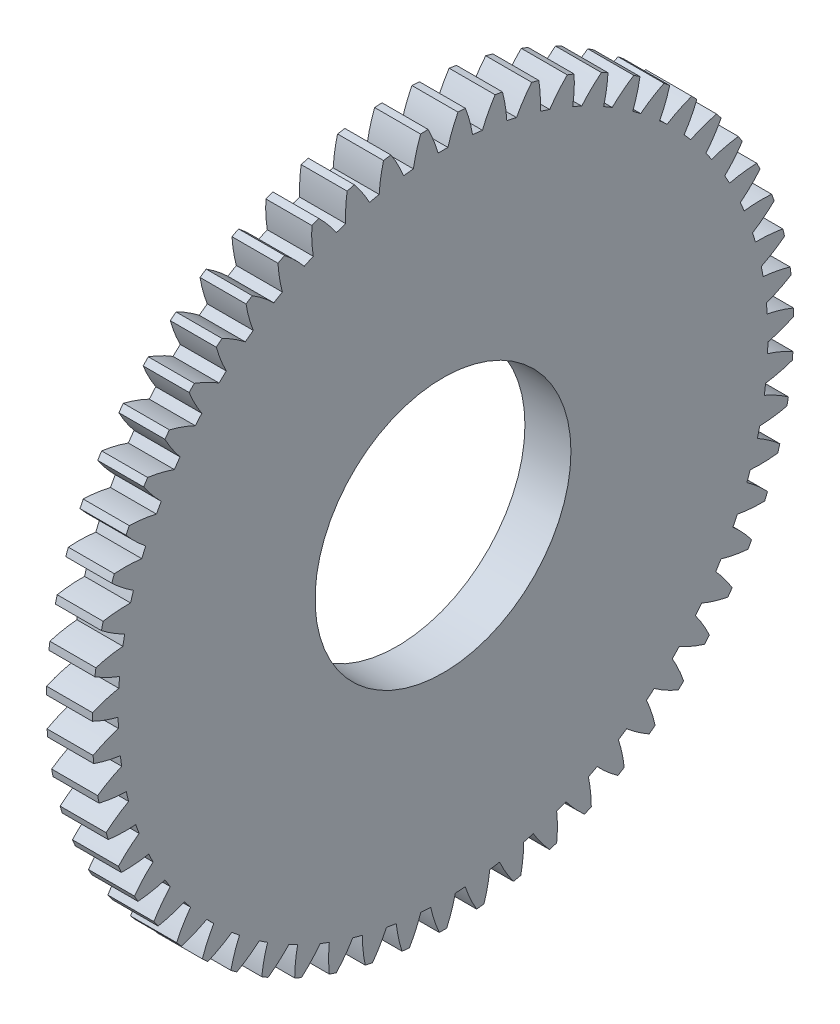
SolidWorks part; units mm, degrees
ref_plane "Plane1" through (0, 0, 0) normal (0, 0, 1) x (1, 0, 0)
ref_plane "Plane2" through (0, 0, 0) normal (0, 1, 0) x (1, 0, 0)
ref_plane "Plane3" through (0, 0, 0) normal (1, 0, 0) x (0, 0, -1)
sketch "HoldingSke" plane through (0, 0, 0) normal (0, 1, 0) x (1, 0, 0)
  line L0 (0, 0) -> (0.515, -0.8572)
  line L1 (-15, 0) -> (100, 0) construction
  line L2 (0, 0) -> (-2.1039, 2.3779)
  line L3 (0, 0) -> (-11.863, 4.5341)
  line L4 (0, 0) -> (4.4479, 7.4025)
  line L5 (0, 0) -> (-46.8476, -17.4728)
  line L6 (0, 0) -> (-3.3159, -2.2372)
  line L7 (-2.1039, 2.3779) -> (8.6586, 51.2059)
  line L8 (-76.2, 54.61) -> (-74.8, 54.61)
  line L9 (-71.009, 38.7566) -> (-53.1078, 45.2721)
  line L10 (-76.2, 71.12) -> (104.1128, 71.12)
  line L11 (0, 0) -> (-4, 0)
  line L12 (-76.2, 101.6) -> (-76.162, 101.6)
  line L13 (24.9733, 27.94) -> (52.9518, 28.4284)
  line L14 (24.9733, 27.94) -> (24.9743, 27.94)
  line L15 (24.9733, 27.94) -> (100.4006, 29.5858)
  line L16 (-63.627, -1) -> (-12.827, -1)
  circle A0 centre (0, 0) radius 4
  circle A1 centre (0, 0) radius 28.249
  circle A2 centre (0, 0) radius 37.5
  circle A3 centre (0, 0) radius 4
  dimension "MHD" = 56.498
  dimension "Hub_dia" = 75
  dimension "Bore" = 8
  dimension "MBD" = 8
  dimension "Num_teeth" = 59
  dimension "Pitch" = 1
  dimension "Overall_len" = 50
  dimension "Show_teeth" = 59
  dimension "Thickness" = 4
  dimension "OAL" = 50.0001
  dimension "T_dim" = 1.4
  dimension "Ap" = 20
  dimension "H" = 19.05
  dimension "Pitch_radius" = 180.3128
  dimension "Width" = 4
  dimension "Backlash" = 0.038
  dimension "Addendum_fac" = 1
  dimension "Dedendum_fac" = 1.25
  dimension "Clearance_fac" = 0.25
  dimension "Dedendum_add" = 0.001
  dimension "Module" = 1
sketch "BasProSke" plane through (0, 0, 0) normal (0, 1, 0) x (1, 0, 0)
  line L0 (-10, 0) -> (60, 0) construction
  line L1 (0, 0) -> (0, 30.5)
  line L2 (0, 0) -> (4, 0)
  line L3 (4, 0) -> (4, 30.5)
  line L4 (4, 30.5) -> (0, 30.5)
  dimension "Thickness" = 4
  dimension "Diameter" = 61
revolve "Base-Revolve" add sketch "BasProSke" angle 360 about L0
sketch "TooCutSke" plane through (0, 0, 0) normal (1, 0, 0) x (0, 0, -1)
  line L1 (0, 0) -> (0, 107) construction
  line L2 (0, 0) -> (-0.8518, 29.4877) construction
  line L3 (0, 0) -> (-3.1392, 58.8989) construction
  line L4 (-0.8518, 29.4877) -> (-1.5696, 29.4494) construction
  arc A0 (0.4308, 28.2457) -> (-0.4308, 28.2457) centre (0, 0) ccw
  arc A1 (1.3141, 30.4971) -> (-1.3141, 30.4971) centre (0, 0) ccw
  circle A2 centre (0, 0) radius 29.5 construction
  circle A3 centre (0, 0) radius 27.7209 construction
  arc A4 (-0.4308, 28.2457) -> (-1.3141, 30.4971) centre (-11.7994, 25.0843) ccw
  arc A5 (1.3141, 30.4971) -> (0.4308, 28.2457) centre (11.7994, 25.0843) ccw
  dimension "Root_dia" = 56.498
  dimension "Overcut_dia" = 61.0508
  dimension "Pitch_dia" = 59
  dimension "Base_dia" = 55.4419
  dimension "Flank_rad" = 11.8
  dimension "Half_ang" = 3.051
  dimension "Half_CT" = 0.7188
extrude "ToothCut" cut sketch "TooCutSke" along normal through all
fillet "Breaks" [suppressed] radius 0.02 tangent propagation no
fillet "RootFillets" [suppressed] radius 0.251
pattern_circular "TeethCuts" count 59 every 6.102 about axis through (-10, 0, 0) along (1, 0, 0) of "ToothCut", "RootFillets", "Breaks"
sketch "HubNeaOneSke" plane through (0, 0, 0) normal (-1, 0, 0) x (0, 0, 1)
  circle A0 centre (0, 0) radius 28.249
  dimension "Diameter" = 56.498
extrude "HubNearOne" [suppressed] add sketch "HubNeaOneSke" along normal blind 46.0001
sketch "HubNeaBotSke" plane through (0, 0, 0) normal (-1, 0, 0) x (0, 0, 1)
  circle A0 centre (0, 0) radius 28.249
  dimension "Diameter" = 56.498
extrude "HubNearBoth" [suppressed] add sketch "HubNeaBotSke" along normal blind 23
ref_plane "FarPln" through (4, 0, 0) normal (1, 0, 0) x (0, 0, -1)
sketch "HubFarSke" plane through (4, 0, 0) normal (1, 0, 0) x (0, 0, -1)
  circle A0 centre (0, 0) radius 28.249
  dimension "Diameter" = 56.498
extrude "HubFar" [suppressed] add sketch "HubFarSke" along normal blind 23
sketch "BorSke" plane through (0, 0, 0) normal (1, 0, 0) x (0, 0, -1)
  circle A0 centre (0, 0) radius 4
  dimension "Diameter" = 8
extrude "Bore" cut sketch "BorSke" along normal mid plane 100.0001
sketch "KeySke" plane through (0, 0, 0) normal (1, 0, 0) x (0, 0, -1)
  line L0 (-1.5, 0) -> (-1.5, 5.4)
  line L1 (-1.5, 5.4) -> (1.5, 5.4)
  line L2 (1.5, 5.4) -> (1.5, 0)
  line L3 (0, 0) -> (0, 34) construction
  line L4 (-1.5, 0) -> (1.5, 0)
  dimension "Offset" = 5.4
  dimension "Width" = 3
extrude "Keyway" [suppressed] cut sketch "KeySke" along normal mid plane 100.0001
pattern_circular "Keyway2" [suppressed] count 2 every 90 about axis through (-10, 0, 0) along (1, 0, 0) reverse direction yes
sketch "Sketch1" plane through (4, 0, 0) normal (1, 0, 0) x (0, 0, -1)
  circle A0 centre (0, 0) radius 11.125
  dimension "D1" = 22.25
extrude "Cut-Extrude1" cut sketch "Sketch1" against normal blind 10
equation "' \"Module@HoldingSke\" = 6.35"
equation "' \"Num_teeth@HoldingSke\" = 12"
equation "' \"Ap@HoldingSke\" =  20"
equation "' \"Ap@HoldingSke\" = 20"
equation "' \"Width@HoldingSke\" = 0.5 * 25.4"
equation "' \"Hub_dia@HoldingSke\"= 1 * 25.4"
equation "' \"Hub_dia@HoldingSke\" = 1 * 25.4"
equation "' \"Overall_len@HoldingSke\" = 1.0 * 25.4"
equation "' \"Bore@HoldingSke\" = 0.75 * 25.4"
equation "' \"T_dim@HoldingSke\" = 0.1 * 25.4"
equation "' \"Width@KeySke\" = 0.25 * 25.4"
equation "' \"Show_teeth@HoldingSke\" = 13"
equation "' \"Backlash@HoldingSke\" = 0.009 * 25.4"
equation "' \"Addendum_fac@HoldingSke\" = 1.0"
equation "' \"Dedendum_fac@HoldingSke\" = 1.25"
equation "' \"Dedendum_add@HoldingSke\" = 0.00005 * 25.4"
equation "' \"Clearance_fac@HoldingSke\" = 0.25"
equation "\"Pitch@HoldingSke\" = 1 / \"Module@HoldingSke\""
equation "\"Overcut_dia@TooCutSke\" = (\"Num_teeth@HoldingSke\" + 2 * \"Addendum_fac@HoldingSke\") / \"Pitch@HoldingSke\" + 0.002 * 25.4"
equation "\"Pitch_dia@TooCutSke\" = \"Num_teeth@HoldingSke\" / \"Pitch@HoldingSke\""
equation "\"Base_dia@TooCutSke\" = \"Num_teeth@HoldingSke\" / \"Pitch@HoldingSke\" * cos((\"Ap@HoldingSke\"  * 3.14159265 / 180))"
equation "\"Root_dia@TooCutSke\" = (\"Num_teeth@HoldingSke\" + 2) / \"Pitch@HoldingSke\" - 2 * (\"Addendum_fac@HoldingSke\" + \"Dedendum_fac@HoldingSke\") / \"Pitch@HoldingSke\" - \"Dedendum_add@HoldingSke\" * 2"
equation "\"Half_ang@TooCutSke\" = 180 / \"Num_teeth@HoldingSke\""
equation "\"Half_CT@TooCutSke\" = \"Num_teeth@HoldingSke\" / \"Pitch@HoldingSke\" * sin((3.14159265 / 2 / \"Num_teeth@HoldingSke\")) / 2 - 7 * \"Backlash@HoldingSke\" / 4"
equation "\"Flank_rad@TooCutSke\" = \"Num_teeth@HoldingSke\" / \"Pitch@HoldingSke\" / 5"
equation "\"Radius@RootFillets\" = \"Clearance_fac@HoldingSke\" / \"Pitch@HoldingSke\" + \"Dedendum_add@HoldingSke\""
equation "\"Break_rad@Breaks\" = 0.02 / \"Pitch@HoldingSke\""
equation "\"Thickness@HoldingSke\" = \"Width@HoldingSke\""
equation "\"OAL@HoldingSke\" = \"Thickness@HoldingSke\""
equation "\"MHD@HoldingSke\" = (\"Num_teeth@HoldingSke\" + 2) / \"Pitch@HoldingSke\" - 2 * (\"Addendum_fac@HoldingSke\" + \"Dedendum_fac@HoldingSke\")  / \"Pitch@HoldingSke\" - \"Dedendum_add@HoldingSke\" * 2"
equation "\"MBD@HoldingSke\" = (\"Num_teeth@HoldingSke\" + 2) / \"Pitch@HoldingSke\" - 2 * (\"Addendum_fac@HoldingSke\" + \"Dedendum_fac@HoldingSke\")  / \"Pitch@HoldingSke\" - \"Dedendum_add@HoldingSke\" * 2 - 0.002 * 25.4"
equation "\"MHD@HoldingSke\" = ((sgn( \"MHD@HoldingSke\" - \"Hub_dia@HoldingSke\" )-1)*( \"MHD@HoldingSke\" - \"Hub_dia@HoldingSke\" ))/-2+ \"Hub_dia@HoldingSke\""
equation "\"MBD@HoldingSke\" = ((sgn( \"MBD@HoldingSke\" - \"Bore@HoldingSke\" )-1)*( \"MBD@HoldingSke\" - \"Bore@HoldingSke\" ))/-2+ \"Bore@HoldingSke\""
equation "\"OAL@HoldingSke\" = ((sgn( \"OAL@HoldingSke\" - \"Overall_len@HoldingSke\" )+1)*( \"OAL@HoldingSke\" - \"Overall_len@HoldingSke\" ))/2 + \"Overall_len@HoldingSke\" + 0.000002 * 25.4"
equation "\"Num_teeth@TeethCuts\" = int( \"Show_teeth@HoldingSke\" ) + 1"
equation "\"Num_teeth@TeethCuts\" = ((sgn( \"Num_teeth@TeethCuts\" - \"Num_teeth@HoldingSke\" )-1)*( \"Num_teeth@TeethCuts\" - \"Num_teeth@HoldingSke\" ))/-2+ \"Num_teeth@HoldingSke\""
equation "\"Num_teeth@TeethCuts\" = ((sgn( \"Num_teeth@TeethCuts\" - 2.0)+1)*( \"Num_teeth@TeethCuts\" - 2.0))/2 +2.0"
equation "\"Angle@TeethCuts\" = 360.0 / \"Num_teeth@HoldingSke\""
equation "\"Diameter@BasProSke\" = (\"Num_teeth@HoldingSke\" + 2 * \"Addendum_fac@HoldingSke\") / \"Pitch@HoldingSke\""
equation "\"Thickness@BasProSke\"  = \"Thickness@HoldingSke\""
equation "' \"Fillet_rad@BasProSke\" =  \"Thickness@HoldingSke\" * 0.05"
equation "' \"Fillet_rad@BasProSke\" = \"Thickness@HoldingSke\" * 0.05"
equation "\"MHD@HoldingSke\" = ((sgn( \"MHD@HoldingSke\" - \"Root_dia@TooCutSke\" )-1)*( \"MHD@HoldingSke\" - \"Root_dia@TooCutSke\" ))/-2+ \"Root_dia@TooCutSke\""
equation "\"Diameter@HubNeaOneSke\" = \"MHD@HoldingSke\""
equation "\"Length@HubNearOne\" = \"OAL@HoldingSke\" - \"Thickness@BasProSke\""
equation "\"Diameter@HubNeaBotSke\" = \"MHD@HoldingSke\""
equation "\"Length@HubNearBoth\" = ( \"OAL@HoldingSke\" - \"Thickness@BasProSke\" ) / 2.0"
equation "\"Thickness@FarPln\" = \"Thickness@BasProSke\""
equation "\"Diameter@HubFarSke\" = \"MHD@HoldingSke\""
equation "\"Length@HubFar\" = ( \"OAL@HoldingSke\" - \"Thickness@BasProSke\" ) / 2.0"
equation "\"Diameter@BorSke\" = \"MBD@HoldingSke\""
equation "\"D1@Bore\" = \"OAL@HoldingSke\" * 2.0"
equation "\"D1@Keyway\" = \"OAL@HoldingSke\" * 2.0"
equation "\"Offset@KeySke\" = \"T_dim@HoldingSke\" + \"MBD@HoldingSke\" / 2.0"
